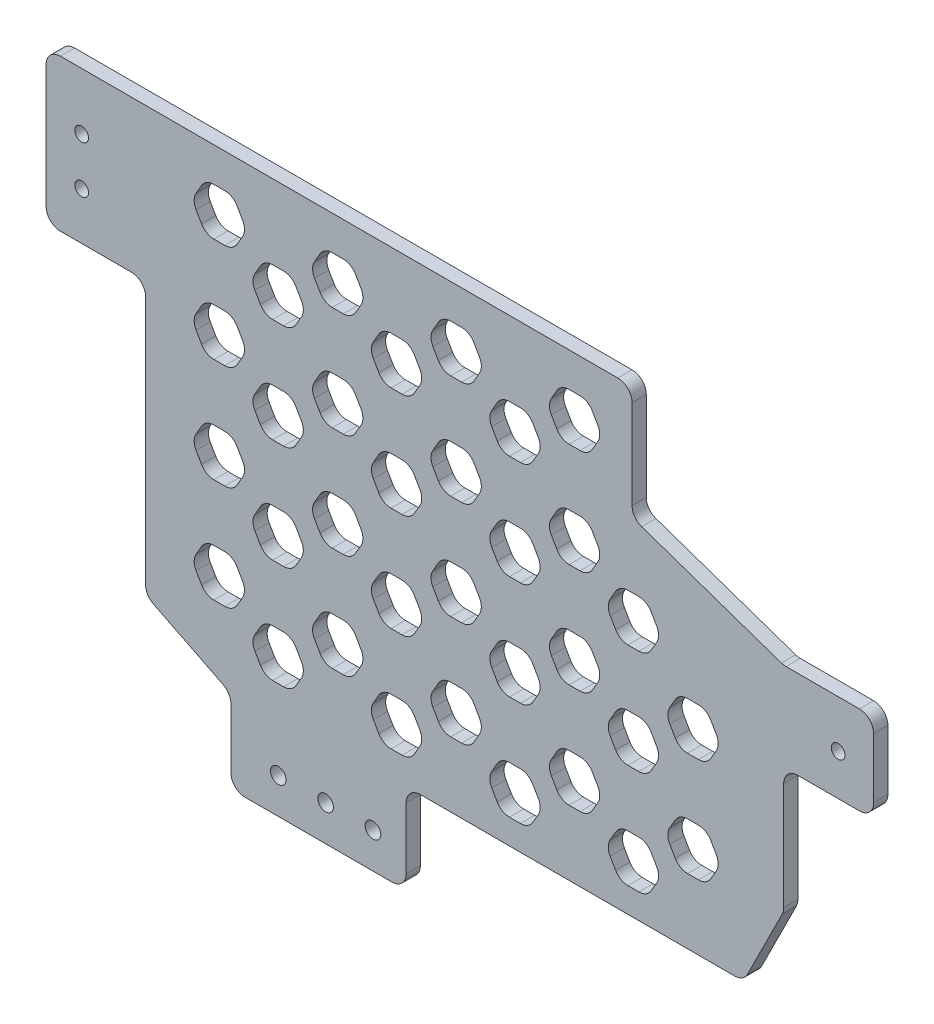
SolidWorks part; units mm, degrees
material "轻木"
ref_plane "前视基准面" through (0, 0, 0) normal (0, 0, 1) x (1, 0, 0)
ref_plane "上视基准面" through (0, 0, 0) normal (0, 1, 0) x (1, 0, 0)
ref_plane "右视基准面" through (0, 0, 0) normal (1, 0, 0) x (0, 0, -1)
other "Configuration Table"
sketch "草图1" plane through (0, 0, 0) normal (0, 0, 1) x (1, 0, 0)
  line L0 (45, -487.5) -> (65, -487.5) construction
  line L1 (415, -487.5) -> (-185, -487.5) construction
  line L2 (65, -487.5) -> (65, -367.5) construction
  line L3 (230, -367.5) -> (0, -367.5) construction
  line L4 (65, -367.5) -> (134.7, -367.5) construction
  line L5 (131.6098, -367.5) -> (70, -367.5) construction
  line L6 (134.7, -367.5) -> (144.6985, -347.503) construction
  line L7 (144.6985, -367.5) -> (144.6985, -7.5) construction
  line L9 (144.6985, -297.5) -> (144.6985, -262.5) construction
  line L10 (144.6985, -262.5) -> (-15, -262.5) construction
  line L11 (-15, -262.5) -> (-15, -302.5) construction
  line L12 (-15, -472.5) -> (-15, 97.5) construction
  line L13 (-15, -302.5) -> (2, -302.5) construction
  line L14 (2, -302.5) -> (2, -347.5) construction
  line L15 (2, -347.5) -> (2, -358.5) construction
  line L16 (17.2361, -366.118) -> (1.0557, -358.0279) construction
  line L17 (2, -358.5) -> (20, -367.5) construction
  line L18 (20, -367.5) -> (20, -382.5) construction
  line L19 (230, -382.5) -> (0, -382.5) construction
  line L20 (20, -382.5) -> (0, -392.5) construction
  line L21 (0, -472.5) -> (0, 97.5) construction
  line L22 (0, -392.5) -> (-15, -392.5) construction
  line L23 (-15, -392.5) -> (-15, -453.5) construction
  line L24 (-15, -453.5) -> (0, -453.5) construction
  line L25 (0, -453.5) -> (0, -470.5) construction
  line L26 (0, -470.5) -> (45, -470.5) construction
  line L27 (45, -470.5) -> (45, -487.5) construction
  line L28 (144.6985, -347.503) -> (144.6985, -324.1459) construction
  line L29 (144.6985, -324.1459) -> (159.7, -324.1459) construction
  line L30 (159.7, -324.1459) -> (159.6985, -297.5) construction
  line L31 (159.6985, -367.5) -> (159.6985, -7.5) construction
  line L32 (159.6985, -297.5) -> (144.6985, -297.5) construction
  line L33 (149.6985, -262.5) -> (158.5181, -262.5) construction
  line L35 (158.5181, -297.5) -> (149.6985, -297.5) construction
  line L36 (143.318, -350.2639) -> (136.082, -364.7361) construction
  line L37 (65, -372.5) -> (65, -482.5) construction
  line L40 (-4, -453.5) -> (-11, -453.5) construction
  line L41 (-10, -392.5) -> (-1.1803, -392.5) construction
  line L42 (1.0557, -391.9721) -> (17.2361, -383.882) construction
  line L43 (140.6985, -301.5) -> (140.6985, -266.5) construction
  line L44 (140.6985, -266.5) -> (-11, -266.5) construction
  line L45 (-11, -266.5) -> (-11, -298.5) construction
  line L46 (-11, -298.5) -> (6, -298.5) construction
  line L47 (6, -298.5) -> (6, -347.5) construction
  line L48 (6, -347.5) -> (6, -356.0279) construction
  line L49 (6, -356.0279) -> (24, -365.0279) construction
  line L50 (24, -365.0279) -> (24, -384.9721) construction
  line L51 (24, -384.9721) -> (0.9443, -396.5) construction
  line L52 (0.9443, -396.5) -> (-11, -396.5) construction
  line L53 (-11, -396.5) -> (-11, -449.5) construction
  line L54 (-11, -449.5) -> (4, -449.5) construction
  line L55 (4, -449.5) -> (4, -466.5) construction
  line L56 (4, -466.5) -> (49, -466.5) construction
  line L57 (49, -466.5) -> (49, -483.5) construction
  line L58 (49, -483.5) -> (61, -483.5) construction
  line L59 (61, -483.5) -> (61, -363.5) construction
  line L60 (61, -363.5) -> (132.2279, -363.5) construction
  line L61 (132.2279, -363.5) -> (140.6985, -346.5588) construction
  line L62 (140.6985, -346.5588) -> (140.6985, -320.1459) construction
  line L63 (140.6985, -320.1459) -> (155.6998, -320.1459) construction
  line L64 (155.6998, -320.1459) -> (155.6987, -301.5) construction
  line L65 (155.6987, -301.5) -> (140.6985, -301.5) construction
  line L66 (-15, -266.5) -> (140.6985, -266.5)
  line L67 (140.6985, -266.5) -> (140.6985, -301.5)
  line L68 (140.6985, -301.5) -> (159.6987, -301.5)
  line L69 (159.6987, -301.5) -> (159.6998, -320.1459)
  line L70 (159.6998, -320.1459) -> (140.6985, -320.1459)
  line L71 (140.6985, -320.1459) -> (140.6985, -346.5588)
  line L72 (140.6985, -346.5588) -> (132.2279, -363.5)
  line L73 (132.2279, -363.5) -> (61, -363.5)
  line L74 (61, -363.5) -> (61, -487.5)
  line L75 (61, -487.5) -> (49, -487.5)
  line L76 (49, -487.5) -> (49, -466.5)
  line L77 (49, -466.5) -> (4, -466.5)
  line L78 (4, -466.5) -> (4, -449.5)
  line L79 (4, -449.5) -> (-15, -449.5)
  line L80 (-15, -449.5) -> (-15, -396.5)
  line L81 (-15, -396.5) -> (0.9443, -396.5)
  line L82 (0.9443, -396.5) -> (24, -384.9721)
  line L83 (24, -384.9721) -> (24, -365.0279)
  line L84 (24, -365.0279) -> (6, -356.0279)
  line L85 (6, -356.0279) -> (6, -298.5)
  line L86 (6, -298.5) -> (-15, -298.5)
  line L87 (-15, -298.5) -> (-15, -266.5)
  dimension "D1" = 4
extrude "凸台-拉伸1" add sketch "草图1" along normal blind 3
sketch "草图2" plane through (0, 0, 3) normal (0, 0, 1) x (1, 0, 0)
  line L2 (-7.5, -251.7939) -> (-7.5, -517.3425) construction
  line L3 (16.6902, -480) -> (92.3332, -480) construction
  line L4 (-15, -298.5) -> (6, -298.5) construction
  line L6 (49, -487.5) -> (61, -487.5) construction
  line L8 (-15, -396.5) -> (-15, -449.5) construction
  line L13 (159.6998, -320.1459) -> (159.6987, -301.5) construction
  line L14 (159.6987, -301.5) -> (140.6985, -301.5) construction
  line L17 (49, -466.5) -> (49, -487.5) construction
  circle A0 centre (-7.5, -415) radius 1.45
  circle A1 centre (-7.5, -439.5) radius 1.45
  circle A2 centre (56, -480) radius 1.45
  circle A5 centre (152.1993, -311.5) radius 1.45
  circle A7 centre (-7.5, -288.5) radius 1.45
  circle A8 centre (-7.5, -278.5) radius 1.45
  dimension "D5" = 126.5
  dimension "D8" = 10
  dimension "D11" = 7
  dimension "D12" = 2.9
  dimension "D13" = 10
  dimension "D14" = 10
  dimension "D3" = 2.9
  dimension "D4" = 24.5
  dimension "D1" = 7.5
  dimension "D2" = 7.5
  dimension "D7" = 7.5
extrude "切除-拉伸1" cut sketch "草图2" against normal through all
sketch "草图3" plane through (0, 0, 3) normal (0, 0, 1) x (1, 0, 0)
  line L0 (140.6985, -301.5) -> (140.6985, -266.5) construction
  line L1 (140.6985, -266.5) -> (108.6985, -266.5)
  line L2 (140.6985, -266.5) -> (140.6985, -301.5)
  line L3 (140.6985, -301.5) -> (108.6985, -290.4655)
  line L4 (108.6985, -266.5) -> (108.6985, -290.4655)
  line L5 (111.6985, -266.5) -> (111.6985, -287.5) construction
  line L6 (111.6985, -287.5) -> (140.6985, -297.5) construction
  line L7 (140.6985, -266.5) -> (-15, -266.5) construction
  dimension "D1" = 3
  dimension "D3" = 21
  dimension "D4" = 10
  dimension "D5" = 29
extrude "切除-拉伸2" cut sketch "草图3" against normal blind 10
fillet "圆角3" radius 3 23 edges at (159.6998, -320.1459, 1.5) (140.6985, -320.1459, 1.5) (61, -487.5, 1.5) (49, -487.5, 1.5) (49, -466.5, 1.5) (4, -466.5, 1.5) (4, -449.5, 1.5) (-15, -449.5, 1.5) (-15, -396.5, 1.5) (0.9443, -396.5, 1.5) (24, -384.9721, 1.5) (24, -365.0279, 1.5) (6, -356.0279, 1.5) (6, -298.5, 1.5) (-15, -298.5, 1.5) (-15, -266.5, 1.5) (159.6987, -301.5, 1.5) (140.6985, -346.5588, 1.5) (132.2279, -363.5, 1.5) (61, -363.5, 1.5) (108.6985, -266.5, 1.5) (108.6985, -290.4655, 1.5) (140.6985, -301.5, 1.5)
sketch "草图4" plane through (0, 0, 3) normal (0, 0, 1) x (1, 0, 0)
  circle A0 centre (54, -375) radius 1.65 construction
  circle A1 centre (44, -375) radius 1.65 construction
  circle A2 centre (34, -375) radius 1.65 construction
  circle A3 centre (54, -375) radius 1.65
  circle A4 centre (44, -375) radius 1.65
  circle A5 centre (34, -375) radius 1.65
extrude "切除-拉伸3" cut sketch "草图4" against normal through all
sketch "草图5" plane through (0, 0, 3) normal (0, 0, 1) x (1, 0, 0)
  line L0 (52.3365, -278.7406) -> (49.4497, -273.7406)
  line L1 (27.3365, -278.7406) -> (24.4497, -273.7406)
  line L2 (24.4497, -273.7406) -> (18.6762, -273.7406)
  line L3 (18.6762, -273.7406) -> (15.7895, -278.7406)
  line L4 (15.7895, -278.7406) -> (18.6762, -283.7406)
  line L5 (18.6762, -283.7406) -> (24.4497, -283.7406)
  line L6 (24.4497, -283.7406) -> (27.3365, -278.7406)
  line L7 (39.7534, -287.2338) -> (36.8666, -282.2338)
  line L8 (36.8666, -282.2338) -> (31.0931, -282.2338)
  line L9 (31.0931, -282.2338) -> (28.2064, -287.2338)
  line L10 (28.2064, -287.2338) -> (31.0931, -292.2338)
  line L11 (31.0931, -292.2338) -> (36.8666, -292.2338)
  line L12 (36.8666, -292.2338) -> (39.7534, -287.2338)
  line L13 (49.4497, -273.7406) -> (43.6762, -273.7406)
  line L14 (43.6762, -273.7406) -> (40.7895, -278.7406)
  line L15 (40.7895, -278.7406) -> (43.6762, -283.7406)
  line L16 (43.6762, -283.7406) -> (49.4497, -283.7406)
  line L17 (49.4497, -283.7406) -> (52.3365, -278.7406)
  line L18 (64.7534, -287.2338) -> (61.8666, -282.2338)
  line L19 (61.8666, -282.2338) -> (56.0931, -282.2338)
  line L20 (56.0931, -282.2338) -> (53.2064, -287.2338)
  line L21 (53.2064, -287.2338) -> (56.0931, -292.2338)
  line L22 (56.0931, -292.2338) -> (61.8666, -292.2338)
  line L23 (61.8666, -292.2338) -> (64.7534, -287.2338)
  line L24 (77.3365, -278.7406) -> (74.4497, -273.7406)
  line L25 (74.4497, -273.7406) -> (68.6762, -273.7406)
  line L26 (68.6762, -273.7406) -> (65.7895, -278.7406)
  line L27 (65.7895, -278.7406) -> (68.6762, -283.7406)
  line L28 (68.6762, -283.7406) -> (74.4497, -283.7406)
  line L29 (74.4497, -283.7406) -> (77.3365, -278.7406)
  line L30 (89.7534, -287.2338) -> (86.8666, -282.2338)
  line L31 (86.8666, -282.2338) -> (81.0931, -282.2338)
  line L32 (81.0931, -282.2338) -> (78.2064, -287.2338)
  line L33 (78.2064, -287.2338) -> (81.0931, -292.2338)
  line L34 (81.0931, -292.2338) -> (86.8666, -292.2338)
  line L35 (86.8666, -292.2338) -> (89.7534, -287.2338)
  line L36 (102.3365, -278.7406) -> (99.4497, -273.7406)
  line L37 (99.4497, -273.7406) -> (93.6762, -273.7406)
  line L38 (93.6762, -273.7406) -> (90.7895, -278.7406)
  line L39 (90.7895, -278.7406) -> (93.6762, -283.7406)
  line L40 (93.6762, -283.7406) -> (99.4497, -283.7406)
  line L41 (99.4497, -283.7406) -> (102.3365, -278.7406)
  line L48 (52.3365, -300.7406) -> (49.4497, -295.7406)
  line L49 (49.4497, -295.7406) -> (43.6762, -295.7406)
  line L50 (43.6762, -295.7406) -> (40.7895, -300.7406)
  line L51 (40.7895, -300.7406) -> (43.6762, -305.7406)
  line L52 (43.6762, -305.7406) -> (49.4497, -305.7406)
  line L53 (49.4497, -305.7406) -> (52.3365, -300.7406)
  line L54 (64.7534, -309.2338) -> (61.8666, -304.2338)
  line L55 (61.8666, -304.2338) -> (56.0931, -304.2338)
  line L56 (56.0931, -304.2338) -> (53.2064, -309.2338)
  line L57 (53.2064, -309.2338) -> (56.0931, -314.2338)
  line L58 (56.0931, -314.2338) -> (61.8666, -314.2338)
  line L59 (61.8666, -314.2338) -> (64.7534, -309.2338)
  line L60 (77.3365, -300.7406) -> (74.4497, -295.7406)
  line L61 (74.4497, -295.7406) -> (68.6762, -295.7406)
  line L62 (68.6762, -295.7406) -> (65.7895, -300.7406)
  line L63 (65.7895, -300.7406) -> (68.6762, -305.7406)
  line L64 (68.6762, -305.7406) -> (74.4497, -305.7406)
  line L65 (74.4497, -305.7406) -> (77.3365, -300.7406)
  line L66 (89.7534, -309.2338) -> (86.8666, -304.2338)
  line L67 (86.8666, -304.2338) -> (81.0931, -304.2338)
  line L68 (81.0931, -304.2338) -> (78.2064, -309.2338)
  line L69 (78.2064, -309.2338) -> (81.0931, -314.2338)
  line L70 (81.0931, -314.2338) -> (86.8666, -314.2338)
  line L71 (86.8666, -314.2338) -> (89.7534, -309.2338)
  line L72 (102.3365, -300.7406) -> (99.4497, -295.7406)
  line L73 (99.4497, -295.7406) -> (93.6762, -295.7406)
  line L74 (93.6762, -295.7406) -> (90.7895, -300.7406)
  line L75 (90.7895, -300.7406) -> (93.6762, -305.7406)
  line L76 (93.6762, -305.7406) -> (99.4497, -305.7406)
  line L77 (99.4497, -305.7406) -> (102.3365, -300.7406)
  line L78 (114.7534, -309.2338) -> (111.8666, -304.2338)
  line L79 (111.8666, -304.2338) -> (106.0931, -304.2338)
  line L80 (106.0931, -304.2338) -> (103.2064, -309.2338)
  line L81 (103.2064, -309.2338) -> (106.0931, -314.2338)
  line L82 (106.0931, -314.2338) -> (111.8666, -314.2338)
  line L83 (111.8666, -314.2338) -> (114.7534, -309.2338)
  line L84 (52.3365, -322.7406) -> (49.4497, -317.7406)
  line L85 (49.4497, -317.7406) -> (43.6762, -317.7406)
  line L86 (43.6762, -317.7406) -> (40.7895, -322.7406)
  line L87 (40.7895, -322.7406) -> (43.6762, -327.7406)
  line L88 (43.6762, -327.7406) -> (49.4497, -327.7406)
  line L89 (49.4497, -327.7406) -> (52.3365, -322.7406)
  line L90 (64.7534, -331.2338) -> (61.8666, -326.2338)
  line L91 (61.8666, -326.2338) -> (56.0931, -326.2338)
  line L92 (56.0931, -326.2338) -> (53.2064, -331.2338)
  line L93 (53.2064, -331.2338) -> (56.0931, -336.2338)
  line L94 (56.0931, -336.2338) -> (61.8666, -336.2338)
  line L95 (61.8666, -336.2338) -> (64.7534, -331.2338)
  line L96 (77.3365, -322.7406) -> (74.4497, -317.7406)
  line L97 (74.4497, -317.7406) -> (68.6762, -317.7406)
  line L98 (68.6762, -317.7406) -> (65.7895, -322.7406)
  line L99 (65.7895, -322.7406) -> (68.6762, -327.7406)
  line L100 (68.6762, -327.7406) -> (74.4497, -327.7406)
  line L101 (74.4497, -327.7406) -> (77.3365, -322.7406)
  line L102 (89.7534, -331.2338) -> (86.8666, -326.2338)
  line L103 (86.8666, -326.2338) -> (81.0931, -326.2338)
  line L104 (81.0931, -326.2338) -> (78.2064, -331.2338)
  line L105 (78.2064, -331.2338) -> (81.0931, -336.2338)
  line L106 (81.0931, -336.2338) -> (86.8666, -336.2338)
  line L107 (86.8666, -336.2338) -> (89.7534, -331.2338)
  line L108 (102.3365, -322.7406) -> (99.4497, -317.7406)
  line L109 (99.4497, -317.7406) -> (93.6762, -317.7406)
  line L110 (93.6762, -317.7406) -> (90.7895, -322.7406)
  line L111 (90.7895, -322.7406) -> (93.6762, -327.7406)
  line L112 (93.6762, -327.7406) -> (99.4497, -327.7406)
  line L113 (99.4497, -327.7406) -> (102.3365, -322.7406)
  line L114 (114.7534, -331.2338) -> (111.8666, -326.2338)
  line L115 (111.8666, -326.2338) -> (106.0931, -326.2338)
  line L116 (106.0931, -326.2338) -> (103.2064, -331.2338)
  line L117 (103.2064, -331.2338) -> (106.0931, -336.2338)
  line L118 (106.0931, -336.2338) -> (111.8666, -336.2338)
  line L119 (111.8666, -336.2338) -> (114.7534, -331.2338)
  line L120 (52.3365, -344.7406) -> (49.4497, -339.7406)
  line L121 (49.4497, -339.7406) -> (43.6762, -339.7406)
  line L122 (43.6762, -339.7406) -> (40.7895, -344.7406)
  line L123 (40.7895, -344.7406) -> (43.6762, -349.7406)
  line L124 (43.6762, -349.7406) -> (49.4497, -349.7406)
  line L125 (49.4497, -349.7406) -> (52.3365, -344.7406)
  line L126 (64.7534, -353.2338) -> (61.8666, -348.2338)
  line L127 (61.8666, -348.2338) -> (56.0931, -348.2338)
  line L128 (56.0931, -348.2338) -> (53.2064, -353.2338)
  line L129 (53.2064, -353.2338) -> (56.0931, -358.2338)
  line L130 (56.0931, -358.2338) -> (61.8666, -358.2338)
  line L131 (61.8666, -358.2338) -> (64.7534, -353.2338)
  line L132 (77.3365, -344.7406) -> (74.4497, -339.7406)
  line L133 (74.4497, -339.7406) -> (68.6762, -339.7406)
  line L134 (68.6762, -339.7406) -> (65.7895, -344.7406)
  line L135 (65.7895, -344.7406) -> (68.6762, -349.7406)
  line L136 (68.6762, -349.7406) -> (74.4497, -349.7406)
  line L137 (74.4497, -349.7406) -> (77.3365, -344.7406)
  line L138 (89.7534, -353.2338) -> (86.8666, -348.2338)
  line L139 (86.8666, -348.2338) -> (81.0931, -348.2338)
  line L140 (81.0931, -348.2338) -> (78.2064, -353.2338)
  line L141 (78.2064, -353.2338) -> (81.0931, -358.2338)
  line L142 (81.0931, -358.2338) -> (86.8666, -358.2338)
  line L143 (86.8666, -358.2338) -> (89.7534, -353.2338)
  line L144 (102.3365, -344.7406) -> (99.4497, -339.7406)
  line L145 (99.4497, -339.7406) -> (93.6762, -339.7406)
  line L146 (93.6762, -339.7406) -> (90.7895, -344.7406)
  line L147 (90.7895, -344.7406) -> (93.6762, -349.7406)
  line L148 (93.6762, -349.7406) -> (99.4497, -349.7406)
  line L149 (99.4497, -349.7406) -> (102.3365, -344.7406)
  line L150 (114.7534, -353.2338) -> (111.8666, -348.2338)
  line L151 (111.8666, -348.2338) -> (106.0931, -348.2338)
  line L152 (106.0931, -348.2338) -> (103.2064, -353.2338)
  line L153 (103.2064, -353.2338) -> (106.0931, -358.2338)
  line L154 (106.0931, -358.2338) -> (111.8666, -358.2338)
  line L155 (111.8666, -358.2338) -> (114.7534, -353.2338)
  line L156 (27.3365, -300.7406) -> (24.4497, -295.7406)
  line L157 (24.4497, -295.7406) -> (18.6762, -295.7406)
  line L158 (18.6762, -295.7406) -> (15.7895, -300.7406)
  line L159 (15.7895, -300.7406) -> (18.6762, -305.7406)
  line L160 (18.6762, -305.7406) -> (24.4497, -305.7406)
  line L161 (24.4497, -305.7406) -> (27.3365, -300.7406)
  line L162 (39.7534, -309.2338) -> (36.8666, -304.2338)
  line L163 (36.8666, -304.2338) -> (31.0931, -304.2338)
  line L164 (31.0931, -304.2338) -> (28.2064, -309.2338)
  line L165 (28.2064, -309.2338) -> (31.0931, -314.2338)
  line L166 (31.0931, -314.2338) -> (36.8666, -314.2338)
  line L167 (36.8666, -314.2338) -> (39.7534, -309.2338)
  line L168 (27.3365, -322.7406) -> (24.4497, -317.7406)
  line L169 (24.4497, -317.7406) -> (18.6762, -317.7406)
  line L170 (18.6762, -317.7406) -> (15.7895, -322.7406)
  line L171 (15.7895, -322.7406) -> (18.6762, -327.7406)
  line L172 (18.6762, -327.7406) -> (24.4497, -327.7406)
  line L173 (24.4497, -327.7406) -> (27.3365, -322.7406)
  line L174 (39.7534, -331.2338) -> (36.8666, -326.2338)
  line L175 (36.8666, -326.2338) -> (31.0931, -326.2338)
  line L176 (31.0931, -326.2338) -> (28.2064, -331.2338)
  line L177 (28.2064, -331.2338) -> (31.0931, -336.2338)
  line L178 (31.0931, -336.2338) -> (36.8666, -336.2338)
  line L179 (36.8666, -336.2338) -> (39.7534, -331.2338)
  line L180 (27.3365, -344.7406) -> (24.4497, -339.7406)
  line L181 (24.4497, -339.7406) -> (18.6762, -339.7406)
  line L182 (18.6762, -339.7406) -> (15.7895, -344.7406)
  line L183 (15.7895, -344.7406) -> (18.6762, -349.7406)
  line L184 (18.6762, -349.7406) -> (24.4497, -349.7406)
  line L185 (24.4497, -349.7406) -> (27.3365, -344.7406)
  line L186 (39.7534, -353.2338) -> (36.8666, -348.2338)
  line L187 (36.8666, -348.2338) -> (31.0931, -348.2338)
  line L188 (31.0931, -348.2338) -> (28.2064, -353.2338)
  line L189 (28.2064, -353.2338) -> (31.0931, -358.2338)
  line L190 (31.0931, -358.2338) -> (36.8666, -358.2338)
  line L191 (36.8666, -358.2338) -> (39.7534, -353.2338)
  line L192 (106.0931, -282.2338) -> (103.2064, -287.2338) [skipped]
  line L193 (103.2064, -287.2338) -> (106.0931, -292.2338) [skipped]
  line L194 (106.0931, -292.2338) -> (111.8666, -292.2338) [skipped]
  line L195 (111.8666, -292.2338) -> (114.7534, -287.2338) [skipped]
  line L196 (114.7534, -287.2338) -> (111.8666, -282.2338) [skipped]
  line L197 (111.8666, -282.2338) -> (106.0931, -282.2338) [skipped]
  line L198 (40.9443, -403.9352) -> (38.0576, -398.9352)
  line L199 (15.9443, -403.9352) -> (13.0576, -398.9352)
  line L200 (13.0576, -398.9352) -> (7.2841, -398.9352)
  line L201 (7.2841, -398.9352) -> (4.3973, -403.9352)
  line L202 (4.3973, -403.9352) -> (7.2841, -408.9352)
  line L203 (7.2841, -408.9352) -> (13.0576, -408.9352)
  line L204 (13.0576, -408.9352) -> (15.9443, -403.9352)
  line L205 (27.8328, -413.3437) -> (24.946, -408.3437)
  line L206 (24.946, -408.3437) -> (19.1725, -408.3437)
  line L207 (19.1725, -408.3437) -> (16.2858, -413.3437)
  line L208 (16.2858, -413.3437) -> (19.1725, -418.3437)
  line L209 (19.1725, -418.3437) -> (24.946, -418.3437)
  line L210 (24.946, -418.3437) -> (27.8328, -413.3437)
  line L211 (38.0576, -398.9352) -> (32.2841, -398.9352)
  line L212 (32.2841, -398.9352) -> (29.3973, -403.9352)
  line L213 (29.3973, -403.9352) -> (32.2841, -408.9352)
  line L214 (32.2841, -408.9352) -> (38.0576, -408.9352)
  line L215 (38.0576, -408.9352) -> (40.9443, -403.9352)
  line L216 (52.8328, -413.3437) -> (49.946, -408.3437)
  line L217 (49.946, -408.3437) -> (44.1725, -408.3437)
  line L218 (44.1725, -408.3437) -> (41.2858, -413.3437)
  line L219 (41.2858, -413.3437) -> (44.1725, -418.3437)
  line L220 (44.1725, -418.3437) -> (49.946, -418.3437)
  line L221 (49.946, -418.3437) -> (52.8328, -413.3437)
  line L222 (40.9443, -423.9352) -> (38.0576, -418.9352)
  line L223 (38.0576, -418.9352) -> (32.2841, -418.9352)
  line L224 (32.2841, -418.9352) -> (29.3973, -423.9352)
  line L225 (29.3973, -423.9352) -> (32.2841, -428.9352)
  line L226 (32.2841, -428.9352) -> (38.0576, -428.9352)
  line L227 (38.0576, -428.9352) -> (40.9443, -423.9352)
  line L228 (52.8328, -433.3437) -> (49.946, -428.3437)
  line L229 (49.946, -428.3437) -> (44.1725, -428.3437)
  line L230 (44.1725, -428.3437) -> (41.2858, -433.3437)
  line L231 (41.2858, -433.3437) -> (44.1725, -438.3437)
  line L232 (44.1725, -438.3437) -> (49.946, -438.3437)
  line L233 (49.946, -438.3437) -> (52.8328, -433.3437)
  line L234 (40.9443, -443.9352) -> (38.0576, -438.9352)
  line L235 (38.0576, -438.9352) -> (32.2841, -438.9352)
  line L236 (32.2841, -438.9352) -> (29.3973, -443.9352)
  line L237 (29.3973, -443.9352) -> (32.2841, -448.9352)
  line L238 (32.2841, -448.9352) -> (38.0576, -448.9352)
  line L239 (38.0576, -448.9352) -> (40.9443, -443.9352)
  line L240 (52.8328, -453.3437) -> (49.946, -448.3437)
  line L241 (49.946, -448.3437) -> (44.1725, -448.3437)
  line L242 (44.1725, -448.3437) -> (41.2858, -453.3437)
  line L243 (41.2858, -453.3437) -> (44.1725, -458.3437)
  line L244 (44.1725, -458.3437) -> (49.946, -458.3437)
  line L245 (49.946, -458.3437) -> (52.8328, -453.3437)
  line L246 (15.9443, -423.9352) -> (13.0576, -418.9352)
  line L247 (13.0576, -418.9352) -> (7.2841, -418.9352)
  line L248 (7.2841, -418.9352) -> (4.3973, -423.9352)
  line L249 (4.3973, -423.9352) -> (7.2841, -428.9352)
  line L250 (7.2841, -428.9352) -> (13.0576, -428.9352)
  line L251 (13.0576, -428.9352) -> (15.9443, -423.9352)
  line L252 (27.8328, -433.3437) -> (24.946, -428.3437)
  line L253 (24.946, -428.3437) -> (19.1725, -428.3437)
  line L254 (19.1725, -428.3437) -> (16.2858, -433.3437)
  line L255 (16.2858, -433.3437) -> (19.1725, -438.3437)
  line L256 (19.1725, -438.3437) -> (24.946, -438.3437)
  line L257 (24.946, -438.3437) -> (27.8328, -433.3437)
  line L258 (15.9443, -443.9352) -> (13.0576, -438.9352)
  line L259 (13.0576, -438.9352) -> (7.2841, -438.9352)
  line L260 (7.2841, -438.9352) -> (4.3973, -443.9352)
  line L261 (4.3973, -443.9352) -> (7.2841, -448.9352)
  line L262 (7.2841, -448.9352) -> (13.0576, -448.9352)
  line L263 (13.0576, -448.9352) -> (15.9443, -443.9352)
  line L264 (27.8328, -453.3437) -> (24.946, -448.3437)
  line L265 (24.946, -448.3437) -> (19.1725, -448.3437)
  line L266 (19.1725, -448.3437) -> (16.2858, -453.3437)
  line L267 (16.2858, -453.3437) -> (19.1725, -458.3437)
  line L268 (19.1725, -458.3437) -> (24.946, -458.3437)
  line L269 (24.946, -458.3437) -> (27.8328, -453.3437)
  line L276 (52.8328, -396.3437) -> (49.946, -391.3437)
  line L277 (49.946, -391.3437) -> (44.1725, -391.3437)
  line L278 (44.1725, -391.3437) -> (41.2858, -396.3437)
  line L279 (41.2858, -396.3437) -> (44.1725, -401.3437)
  line L280 (44.1725, -401.3437) -> (49.946, -401.3437)
  line L281 (49.946, -401.3437) -> (52.8328, -396.3437)
  line L282 (127.3365, -322.7406) -> (124.4497, -317.7406)
  line L283 (124.4497, -317.7406) -> (118.6762, -317.7406)
  line L284 (118.6762, -317.7406) -> (115.7895, -322.7406)
  line L285 (115.7895, -322.7406) -> (118.6762, -327.7406)
  line L286 (118.6762, -327.7406) -> (124.4497, -327.7406)
  line L287 (124.4497, -327.7406) -> (127.3365, -322.7406)
  line L288 (127.3365, -344.7406) -> (124.4497, -339.7406)
  line L289 (124.4497, -339.7406) -> (118.6762, -339.7406)
  line L290 (118.6762, -339.7406) -> (115.7895, -344.7406)
  line L291 (115.7895, -344.7406) -> (118.6762, -349.7406)
  line L292 (118.6762, -349.7406) -> (124.4497, -349.7406)
  line L293 (124.4497, -349.7406) -> (127.3365, -344.7406)
  line L294 (40.9443, -386.9352) -> (38.0576, -381.9352) [skipped]
  line L295 (38.0576, -381.9352) -> (32.2841, -381.9352) [skipped]
  line L296 (32.2841, -381.9352) -> (29.3973, -386.9352) [skipped]
  line L297 (29.3973, -386.9352) -> (32.2841, -391.9352) [skipped]
  line L298 (32.2841, -391.9352) -> (38.0576, -391.9352) [skipped]
  line L299 (38.0576, -391.9352) -> (40.9443, -386.9352) [skipped]
  circle A0 centre (21.563, -278.7406) radius 5 construction
  circle A1 centre (33.9799, -287.2338) radius 5 construction
  circle A2 centre (10.1708, -403.9352) radius 5 construction
  circle A3 centre (22.0593, -413.3437) radius 5 construction
  dimension "D1" = 10
  dimension "D2" = 10
  dimension "D6" = 10
  dimension "D7" = 10
  dimension "D3" = 5
  dimension "D8" = 5
  dimension "D4" = 4
  dimension "D5" = 4
  dimension "D9" = 2
  dimension "D10" = 3
  dimension "D11" = 2
  dimension "D12" = 2
extrude "切除-拉伸4" cut sketch "草图5" against normal through all
fillet "圆角4" radius 3 276 edges at (24.4497, -283.7406, 1.5) (18.6762, -283.7406, 1.5) (15.7895, -278.7406, 1.5) (24.4497, -273.7406, 1.5) (27.3365, -278.7406, 1.5) (49.946, -438.3437, 1.5) (44.1725, -438.3437, 1.5) (41.2858, -433.3437, 1.5) (44.1725, -428.3437, 1.5) (49.946, -428.3437, 1.5) (52.8328, -433.3437, 1.5) (38.0576, -448.9352, 1.5) (32.2841, -448.9352, 1.5) (29.3973, -443.9352, 1.5) (32.2841, -438.9352, 1.5) (38.0576, -438.9352, 1.5) (40.9443, -443.9352, 1.5) (49.946, -458.3437, 1.5) (44.1725, -458.3437, 1.5) (41.2858, -453.3437, 1.5) (44.1725, -448.3437, 1.5) (49.946, -448.3437, 1.5) (52.8328, -453.3437, 1.5) (13.0576, -428.9352, 1.5) (7.2841, -428.9352, 1.5) (4.3973, -423.9352, 1.5) (7.2841, -418.9352, 1.5) (13.0576, -418.9352, 1.5) (15.9443, -423.9352, 1.5) (38.0576, -408.9352, 1.5) (32.2841, -408.9352, 1.5) (29.3973, -403.9352, 1.5) (32.2841, -398.9352, 1.5) (38.0576, -398.9352, 1.5) (40.9443, -403.9352, 1.5) (49.946, -418.3437, 1.5) (44.1725, -418.3437, 1.5) (41.2858, -413.3437, 1.5) (44.1725, -408.3437, 1.5) (49.946, -408.3437, 1.5) (52.8328, -413.3437, 1.5) (38.0576, -428.9352, 1.5) (32.2841, -428.9352, 1.5) (29.3973, -423.9352, 1.5) (32.2841, -418.9352, 1.5) (38.0576, -418.9352, 1.5) (40.9443, -423.9352, 1.5) (49.946, -401.3437, 1.5) (44.1725, -401.3437, 1.5) (41.2858, -396.3437, 1.5) (44.1725, -391.3437, 1.5) (49.946, -391.3437, 1.5) (52.8328, -396.3437, 1.5) (24.946, -458.3437, 1.5) (19.1725, -458.3437, 1.5) (16.2858, -453.3437, 1.5) (19.1725, -448.3437, 1.5) (24.946, -448.3437, 1.5) (27.8328, -453.3437, 1.5) (13.0576, -448.9352, 1.5) (7.2841, -448.9352, 1.5) (4.3973, -443.9352, 1.5) (7.2841, -438.9352, 1.5) (13.0576, -438.9352, 1.5) (15.9443, -443.9352, 1.5) (24.946, -438.3437, 1.5) (19.1725, -438.3437, 1.5) (16.2858, -433.3437, 1.5) (19.1725, -428.3437, 1.5) (24.946, -428.3437, 1.5) (27.8328, -433.3437, 1.5) (124.4497, -327.7406, 1.5) (118.6762, -327.7406, 1.5) (115.7895, -322.7406, 1.5) (118.6762, -317.7406, 1.5) (124.4497, -317.7406, 1.5) (127.3365, -322.7406, 1.5) (124.4497, -349.7406, 1.5) (118.6762, -349.7406, 1.5) (115.7895, -344.7406, 1.5) (118.6762, -339.7406, 1.5) (124.4497, -339.7406, 1.5) (127.3365, -344.7406, 1.5) (61.8666, -314.2338, 1.5) (56.0931, -314.2338, 1.5) (53.2064, -309.2338, 1.5) (56.0931, -304.2338, 1.5) (61.8666, -304.2338, 1.5) (64.7534, -309.2338, 1.5) (74.4497, -305.7406, 1.5) (68.6762, -305.7406, 1.5) (65.7895, -300.7406, 1.5) (68.6762, -295.7406, 1.5) (74.4497, -295.7406, 1.5) (77.3365, -300.7406, 1.5) (86.8666, -314.2338, 1.5) (81.0931, -314.2338, 1.5) (78.2064, -309.2338, 1.5) (81.0931, -304.2338, 1.5) (86.8666, -304.2338, 1.5) (89.7534, -309.2338, 1.5) (99.4497, -305.7406, 1.5) (93.6762, -305.7406, 1.5) (90.7895, -300.7406, 1.5) (93.6762, -295.7406, 1.5) (99.4497, -295.7406, 1.5) (102.3365, -300.7406, 1.5) (74.4497, -327.7406, 1.5) (68.6762, -327.7406, 1.5) (65.7895, -322.7406, 1.5) (68.6762, -317.7406, 1.5) (74.4497, -317.7406, 1.5) (77.3365, -322.7406, 1.5) (61.8666, -336.2338, 1.5) (56.0931, -336.2338, 1.5) (53.2064, -331.2338, 1.5) (56.0931, -326.2338, 1.5) (61.8666, -326.2338, 1.5) (64.7534, -331.2338, 1.5) (49.4497, -327.7406, 1.5) (43.6762, -327.7406, 1.5) (40.7895, -322.7406, 1.5) (43.6762, -317.7406, 1.5) (49.4497, -317.7406, 1.5) (52.3365, -322.7406, 1.5) (111.8666, -314.2338, 1.5) (106.0931, -314.2338, 1.5) (103.2064, -309.2338, 1.5) (106.0931, -304.2338, 1.5) (111.8666, -304.2338, 1.5) (114.7534, -309.2338, 1.5) (49.4497, -283.7406, 1.5) (43.6762, -283.7406, 1.5) (40.7895, -278.7406, 1.5) (49.4497, -273.7406, 1.5) (52.3365, -278.7406, 1.5) (36.8666, -292.2338, 1.5) (31.0931, -292.2338, 1.5) (28.2064, -287.2338, 1.5) (31.0931, -282.2338, 1.5) (36.8666, -282.2338, 1.5) (39.7534, -287.2338, 1.5) (61.8666, -292.2338, 1.5) (56.0931, -292.2338, 1.5) (53.2064, -287.2338, 1.5) (56.0931, -282.2338, 1.5) (61.8666, -282.2338, 1.5) (64.7534, -287.2338, 1.5) (74.4497, -283.7406, 1.5) (68.6762, -283.7406, 1.5) (65.7895, -278.7406, 1.5) (68.6762, -273.7406, 1.5) (74.4497, -273.7406, 1.5) (77.3365, -278.7406, 1.5) (86.8666, -292.2338, 1.5) (81.0931, -292.2338, 1.5) (78.2064, -287.2338, 1.5) (81.0931, -282.2338, 1.5) (86.8666, -282.2338, 1.5) (89.7534, -287.2338, 1.5) (99.4497, -283.7406, 1.5) (93.6762, -283.7406, 1.5) (90.7895, -278.7406, 1.5) (93.6762, -273.7406, 1.5) (99.4497, -273.7406, 1.5) (102.3365, -278.7406, 1.5) (13.0576, -408.9352, 1.5) (7.2841, -408.9352, 1.5) (4.3973, -403.9352, 1.5) (7.2841, -398.9352, 1.5) (13.0576, -398.9352, 1.5) (15.9443, -403.9352, 1.5) (49.4497, -305.7406, 1.5) (43.6762, -305.7406, 1.5) (40.7895, -300.7406, 1.5) (43.6762, -295.7406, 1.5) (49.4497, -295.7406, 1.5) (52.3365, -300.7406, 1.5) (24.4497, -327.7406, 1.5) (18.6762, -327.7406, 1.5) (15.7895, -322.7406, 1.5) (18.6762, -317.7406, 1.5) (24.4497, -317.7406, 1.5) (27.3365, -322.7406, 1.5) (36.8666, -314.2338, 1.5) (31.0931, -314.2338, 1.5) (28.2064, -309.2338, 1.5) (31.0931, -304.2338, 1.5) (36.8666, -304.2338, 1.5) (39.7534, -309.2338, 1.5) (24.4497, -305.7406, 1.5) (18.6762, -305.7406, 1.5) (15.7895, -300.7406, 1.5) (18.6762, -295.7406, 1.5) (24.4497, -295.7406, 1.5) (27.3365, -300.7406, 1.5) (111.8666, -358.2338, 1.5) (106.0931, -358.2338, 1.5) (103.2064, -353.2338, 1.5) (106.0931, -348.2338, 1.5) (111.8666, -348.2338, 1.5) (114.7534, -353.2338, 1.5) (24.946, -418.3437, 1.5) (19.1725, -418.3437, 1.5) (16.2858, -413.3437, 1.5) (19.1725, -408.3437, 1.5) (24.946, -408.3437, 1.5) (27.8328, -413.3437, 1.5) (36.8666, -358.2338, 1.5) (31.0931, -358.2338, 1.5) (28.2064, -353.2338, 1.5) (31.0931, -348.2338, 1.5) (36.8666, -348.2338, 1.5) (39.7534, -353.2338, 1.5) (24.4497, -349.7406, 1.5) (18.6762, -349.7406, 1.5) (15.7895, -344.7406, 1.5) (18.6762, -339.7406, 1.5) (24.4497, -339.7406, 1.5) (27.3365, -344.7406, 1.5) (36.8666, -336.2338, 1.5) (31.0931, -336.2338, 1.5) (28.2064, -331.2338, 1.5) (31.0931, -326.2338, 1.5) (36.8666, -326.2338, 1.5) (39.7534, -331.2338, 1.5) (49.4497, -349.7406, 1.5) (43.6762, -349.7406, 1.5) (40.7895, -344.7406, 1.5) (43.6762, -339.7406, 1.5) (49.4497, -339.7406, 1.5) (52.3365, -344.7406, 1.5) (111.8666, -336.2338, 1.5) (106.0931, -336.2338, 1.5) (103.2064, -331.2338, 1.5) (106.0931, -326.2338, 1.5) (111.8666, -326.2338, 1.5) (114.7534, -331.2338, 1.5) (99.4497, -327.7406, 1.5) (93.6762, -327.7406, 1.5) (90.7895, -322.7406, 1.5) (93.6762, -317.7406, 1.5) (99.4497, -317.7406, 1.5) (102.3365, -322.7406, 1.5) (86.8666, -336.2338, 1.5) (81.0931, -336.2338, 1.5) (78.2064, -331.2338, 1.5) (81.0931, -326.2338, 1.5) (86.8666, -326.2338, 1.5) (89.7534, -331.2338, 1.5) (61.8666, -358.2338, 1.5) (56.0931, -358.2338, 1.5) (53.2064, -353.2338, 1.5) (56.0931, -348.2338, 1.5) (61.8666, -348.2338, 1.5) (64.7534, -353.2338, 1.5) (74.4497, -349.7406, 1.5) (68.6762, -349.7406, 1.5) (65.7895, -344.7406, 1.5) (68.6762, -339.7406, 1.5) (74.4497, -339.7406, 1.5) (77.3365, -344.7406, 1.5) (86.8666, -358.2338, 1.5) (81.0931, -358.2338, 1.5) (78.2064, -353.2338, 1.5) (81.0931, -348.2338, 1.5) (86.8666, -348.2338, 1.5) (89.7534, -353.2338, 1.5) (99.4497, -349.7406, 1.5) (93.6762, -349.7406, 1.5) (90.7895, -344.7406, 1.5) (93.6762, -339.7406, 1.5) (99.4497, -339.7406, 1.5) (102.3365, -344.7406, 1.5) (43.6762, -273.7406, 1.5) (18.6762, -273.7406, 1.5)
sketch "草图8" plane through (0, 0, 3) normal (0, 0, 1) x (1, 0, 0)
  line L1 (-19.4755, -382.5) -> (92.3459, -382.5)
  line L2 (-19.4755, -382.5) -> (-19.4755, -489.3028)
  line L3 (-19.4755, -489.3028) -> (92.3459, -489.3028)
  line L4 (92.3459, -382.5) -> (92.3459, -489.3028)
  circle A0 centre (44, -375) radius 1.65 construction
  dimension "D1" = 7.5
extrude "切除-拉伸5" cut sketch "草图8" against normal through all
fillet "圆角5" radius 3 2 edges at (61, -382.5, 1.5) (24, -382.5, 1.5)
